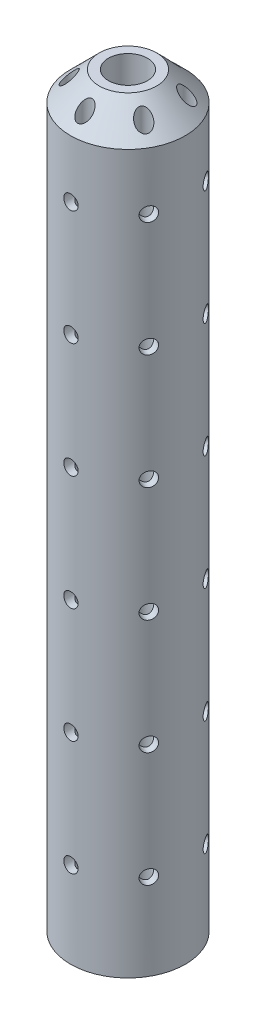
SolidWorks part; units mm, degrees
ref_plane "Front Plane" through (0, 0, 0) normal (0, 0, 1) x (1, 0, 0)
ref_plane "Top Plane" through (0, 0, 0) normal (0, 1, 0) x (1, 0, 0)
ref_plane "Right Plane" through (0, 0, 0) normal (1, 0, 0) x (0, 0, -1)
sketch "Sketch1" plane through (0, 0, 0) normal (0, 1, 0) x (1, 0, 0)
  line L1 (3.6955, 0) -> (1.8478, 3.2004)
  line L2 (1.8478, 3.2004) -> (-1.8478, 3.2004)
  line L3 (-1.8478, 3.2004) -> (-3.6955, 0)
  line L4 (-3.6955, 0) -> (-1.8478, -3.2004)
  line L5 (-1.8478, -3.2004) -> (1.8478, -3.2004)
  line L6 (1.8478, -3.2004) -> (3.6955, 0)
  circle A0 centre (0, 0) radius 3.2004 construction
  circle A1 centre (0, 0) radius 6.35
  dimension "D1" = 6.4008
  dimension "D2" = 12.7
extrude "Boss-Extrude1" add sketch "Sketch1" along normal blind 79.375
sketch "Sketch2" plane through (0, 79.375, 0) normal (0, 1, 0) x (1, 0, 0)
  circle A1 centre (0, 0) radius 2.159
  circle A2 centre (0, 0) radius 6.35
  circle A3 centre (0, 0) radius 6.35
  dimension "D2" = 4.318
  dimension "D1" = 0
extrude "Boss-Extrude2" add sketch "Sketch2" along normal blind 3.175
chamfer "Chamfer1" distance 3.175 distance2 3.175 1 edges at (0, 82.55, 6.35)
sketch "Sketch4" plane through (0, 0, 0) normal (0, -1, 0) x (1, 0, 0)
  circle A0 centre (0, 4.7625) radius 0.7938
  dimension "D2" = 1.5875
  dimension "D1" = 4.7625
extrude "Cut-Extrude1" cut sketch "Sketch4" against normal blind 85.725
ref_plane "Plane1" through (0, 0, 12.7) normal (0, 0, 1) x (1, 0, 0)
sketch "Sketch3" plane through (0, 0, 12.7) normal (0, 0, 1) x (1, 0, 0)
  line L0 (-6.35, 79.375) -> (6.35, 79.375) construction
  line L1 (0, 73.025) -> (0, 60.325) construction
  circle A0 centre (0, 73.025) radius 0.7937
  circle A1 centre (0, 60.325) radius 0.7937
  circle A2 centre (0, 47.625) radius 0.7937
  circle A3 centre (0, 34.925) radius 0.7937
  circle A4 centre (0, 22.225) radius 0.7937
  circle A5 centre (0, 9.525) radius 0.7937
  circle A6 centre (0, -3.175) radius 0.7938
  dimension "D2" = 1.5875
  dimension "D1" = 6.35
  dimension "D4" = 12.7
  dimension "D3" = 7
extrude "Cut-Extrude2" cut sketch "Sketch3" against normal up to surface (7.9375 mm away) up to face at (0.7806, 81.041, 4.6185)
pattern_circular "CirPattern1" count 6 over 360 about axis through (0, 82.55, 0) along (0, 1, 0) of "Cut-Extrude1", "Cut-Extrude2"
